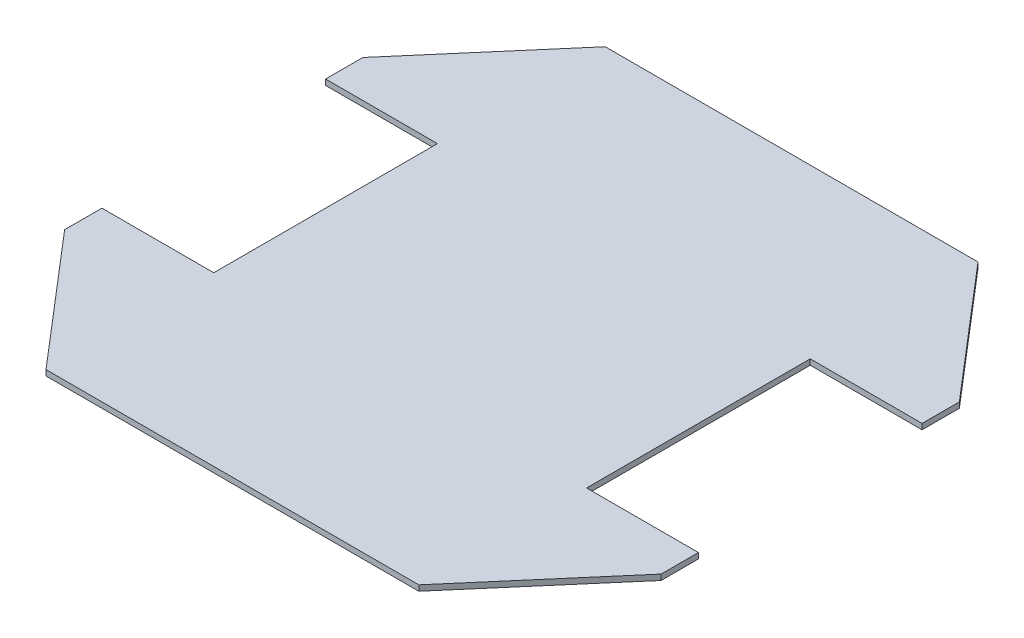
SolidWorks part; units mm, degrees
ref_plane "Front Plane" through (0, 0, 0) normal (0, 0, 1) x (1, 0, 0)
ref_plane "Top Plane" through (0, 0, 0) normal (0, 1, 0) x (1, 0, 0)
ref_plane "Right Plane" through (0, 0, 0) normal (1, 0, 0) x (0, 0, -1)
sketch "Sketch1" plane through (0, 0, 0) normal (0, 1, 0) x (1, 0, 0)
  line L0 (-100, 150) -> (100, 150)
  line L1 (100, 150) -> (160, 80)
  line L2 (160, 80) -> (160, 60)
  line L3 (160, 60) -> (100, 60)
  line L4 (100, 60) -> (100, -60)
  line L5 (100, -60) -> (160, -60)
  line L6 (160, -60) -> (160, -80)
  line L7 (160, -80) -> (100, -150)
  line L8 (100, -150) -> (-100, -150)
  line L9 (-100, -150) -> (-160, -80)
  line L10 (-160, -80) -> (-160, -60)
  line L11 (-160, -60) -> (-100, -60)
  line L12 (-100, -60) -> (-100, 60)
  line L13 (-100, 60) -> (-160, 60)
  line L14 (-160, 60) -> (-160, 80)
  line L15 (-160, 80) -> (-100, 150)
  point P12 (130, -60)
  point P18 (-160, 70)
  point P19 (160, 70)
  point P20 (-160, -70)
  point P21 (160, -70)
  dimension "D1" = 200
  dimension "D2" = 300
  dimension "D3" = 200
  dimension "D4" = 120
  dimension "D5" = 20
  dimension "D6" = 20
  dimension "D7" = 90
  dimension "D8" = 150
  dimension "D9" = 90
  dimension "D10" = 20
  dimension "D11" = 120
  dimension "D12" = 20
  dimension "D13" = 200
  dimension "D14" = 100
  dimension "D15" = 320
  dimension "D16" = 320
  dimension "D17" = 60
  dimension "D18" = 60
  dimension "D19" = 60
extrude "Boss-Extrude1" add sketch "Sketch1" along normal blind 3
